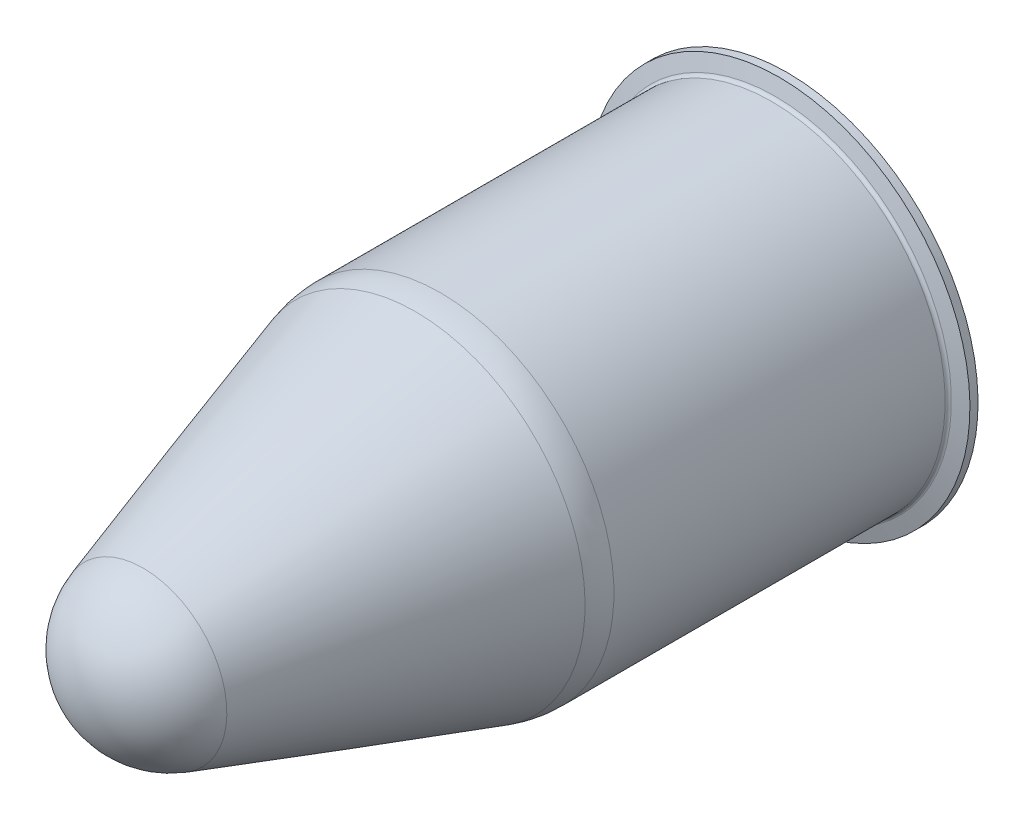
SolidWorks part; units mm, degrees
ref_plane "Front Plane" through (0, 0, 0) normal (0, 0, 1) x (1, 0, 0)
ref_plane "Top Plane" through (0, 0, 0) normal (0, 1, 0) x (1, 0, 0)
ref_plane "Right Plane" through (0, 0, 0) normal (1, 0, 0) x (0, 0, -1)
ref_axis "Axis1" through (0, 0, 216.21) along (0, 0, 1)
sketch "Sketch1" plane through (0, 0, 0) normal (1, 0, 0) x (0, 0, -1)
  line L0 (0, 0) -> (-132.842, 0) construction
  line L1 (0, 145.188) -> (0, 165)
  line L2 (0, 165) -> (-7, 165)
  line L3 (-7, 165) -> (-10.3887, 152.3532)
  line L4 (-132.842, 0) -> (-446.101, 282.0596) construction
  line L5 (-13.4555, 150) -> (-300, 150)
  line L6 (-216.21, 0) -> (-394.19, 0) construction
  line L7 (-7, 145.188) -> (0, 145.188)
  line L8 (-7, 145.188) -> (-10.3887, 145)
  line L9 (-10.3887, 145) -> (-300.1542, 145)
  line L10 (-321.6744, 146.7144) -> (-459.6157, 103.1741) construction
  line L15 (-610, 0) -> (-608.984, 0)
  arc A0 (-557.2285, 72.3632) -> (-610, 0) centre (-534, 0) ccw
  arc A1 (-10.3887, 152.3532) -> (-13.4555, 150) centre (-13.4555, 153.175) cw
  arc A2 (-321.6744, 146.7144) -> (-557.2285, 72.3632) centre (7205.9874, -24112.1872) ccw
  arc A3 (-321.6744, 141.898) -> (-555.8682, 71.7244) centre (6851.7284, -24224.1089) ccw
  arc A4 (-555.8682, 71.7244) -> (-608.984, 0) centre (-534, 0) ccw
  arc A5 (-321.6744, 146.7144) -> (-300, 150) centre (-300, 76.8659) cw
  arc A6 (-300.1542, 145) -> (-321.6744, 141.898) centre (-300.1542, 68.8) ccw
  dimension "D1" = 76
  dimension "D9" = 76.2
  dimension "D11" = 19.812
  dimension "D12" = 132.842
  dimension "D13" = 1.016
  dimension "D14" = 300
  dimension "D2" = 610
  dimension "D4" = 3.175
  dimension "D10" = 4.6
  dimension "D16" = 17.518
  dimension "D3" = 330
  dimension "D5" = 7
  dimension "D6" = 15
  dimension "D7" = 290
  dimension "D8" = 5
  dimension "D15" = 42
  dimension "D18" = 300
revolve "Revolve2" add sketch "Sketch1" angle 360 about L0
sketch "Sketch2" plane through (0, 0, 0) normal (1, 0, 0) x (0, 0, -1)
  line L0 (-37.5685, 0) -> (-356.6069, -287.2635) construction
  line L1 (-216.21, 0) -> (-394.19, 0) construction
  dimension "D1" = 42
sketch "Sketch3" plane through (0, 0, 0) normal (0, 1, 0) x (1, 0, 0)
  line L1 (0, -635.1847) -> (366.0675, -635.1847)
  line L2 (0, -635.1847) -> (0, 107.9387)
  line L3 (0, 107.9387) -> (366.0675, 107.9387)
  line L4 (366.0675, -635.1847) -> (366.0675, 107.9387)
extrude "Extrude1" [suppressed] cut sketch "Sketch3" against normal mid plane 533.4
